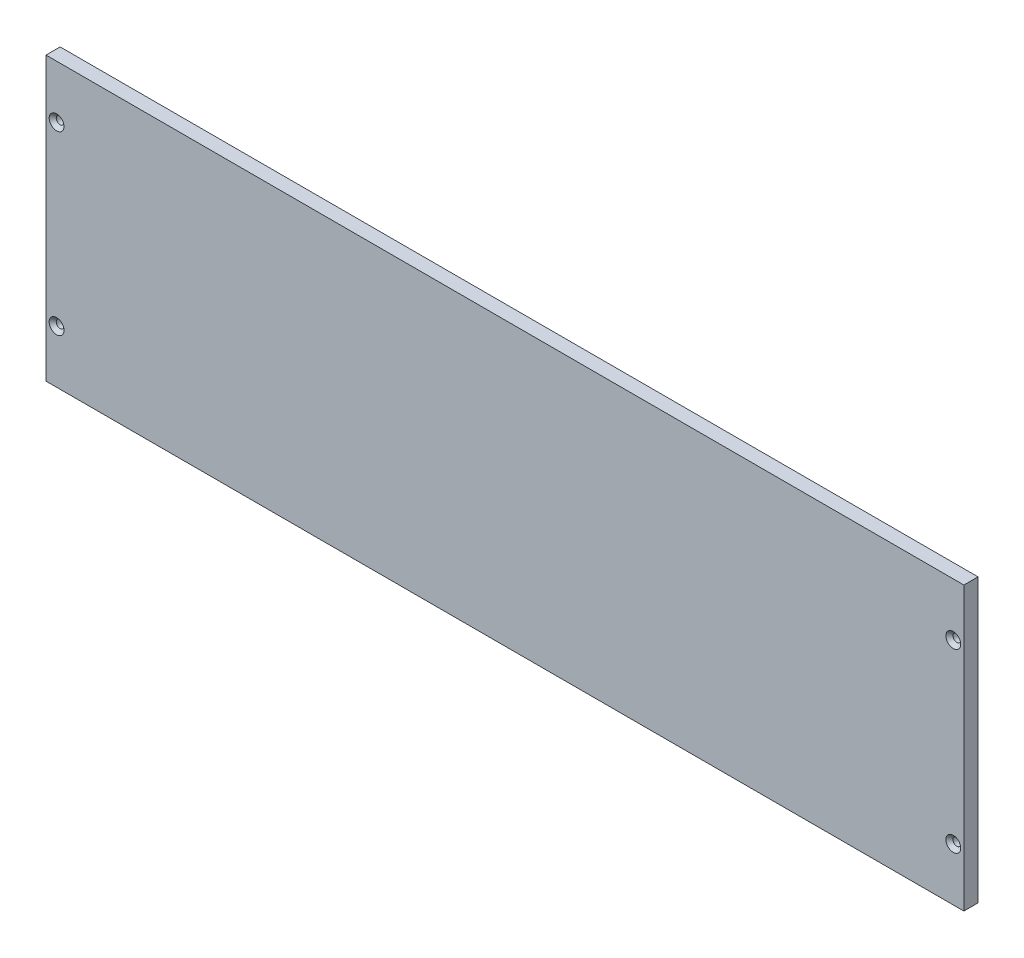
SolidWorks part; units mm, degrees
ref_plane "Plan de face" through (0, 0, 0) normal (0, 0, 1) x (1, 0, 0)
ref_plane "Plan de dessus" through (0, 0, 0) normal (0, 1, 0) x (1, 0, 0)
ref_plane "Plan de droite" through (0, 0, 0) normal (1, 0, 0) x (0, 0, -1)
sketch "Esquisse1" plane through (0, 0, 0) normal (0, 0, 1) x (1, 0, 0)
  line L1 (0, 0) -> (650, 0)
  line L2 (0, 0) -> (0, 200)
  line L3 (0, 200) -> (650, 200)
  line L4 (650, 0) -> (650, 200)
  dimension "D1" = 200
  dimension "D2" = 650
extrude "Boss.-Extru.1" add sketch "Esquisse1" along normal blind 10
sketch "Esquisse2" plane through (0, 0, 10) normal (0, 0, 1) x (1, 0, 0)
  line L0 (0, 200) -> (0, 0) construction
  line L1 (650, 200) -> (0, 200) construction
  line L2 (0, 0) -> (650, 0) construction
  line L3 (650, 0) -> (650, 200) construction
  circle A0 centre (7.5, 162.5) radius 2.75
  circle A1 centre (642.5, 162.5) radius 2.75
  circle A2 centre (7.5, 37.5) radius 2.75
  circle A3 centre (642.5, 37.5) radius 2.75
  point P12 (0, 0)
  dimension "D1" = 5.5
  dimension "D2" = 5.5
  dimension "D3" = 5.5
  dimension "D4" = 5.5
  dimension "D5" = 7.5
  dimension "D6" = 7.5
  dimension "D7" = 37.5
  dimension "D8" = 37.5
  dimension "D9" = 37.5
  dimension "D10" = 37.5
  dimension "D11" = 7.5
  dimension "D12" = 7.5
extrude "Enlèv. mat.-Extru.1" cut sketch "Esquisse2" against normal blind 10
chamfer "Chanfrein1" distance 2.5 angle 45 4 edges at (10.25, 162.5, 10) (10.25, 37.5, 10) (645.25, 37.5, 10) (645.25, 162.5, 10)
